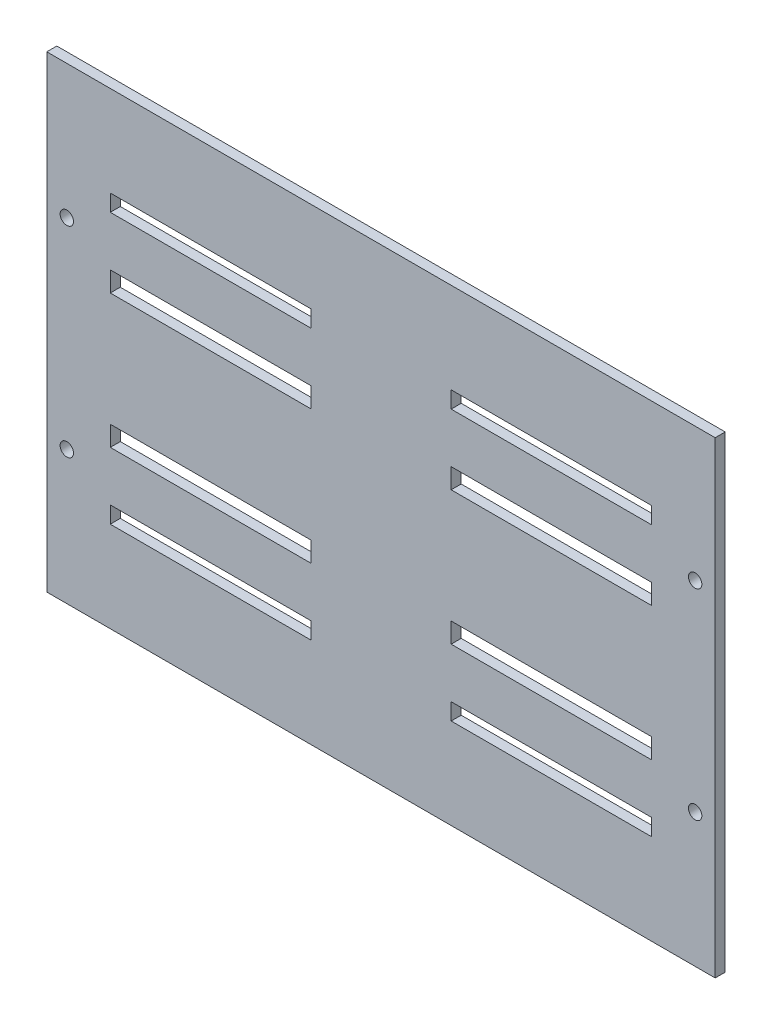
SolidWorks part; units mm, degrees
ref_plane "Front" through (0, 0, 0) normal (0, 0, 1) x (1, 0, 0)
ref_plane "Top" through (0, 0, 0) normal (0, 1, 0) x (1, 0, 0)
ref_plane "Right" through (0, 0, 0) normal (1, 0, 0) x (0, 0, -1)
sketch "草图2" plane through (0, 0, 0) normal (0, 0, 1) x (1, 0, 0)
  line L1 (-100, -70) -> (100, -70)
  line L2 (-100, -70) -> (-100, 70)
  line L3 (-100, 70) -> (100, 70)
  line L4 (100, -70) -> (100, 70)
  line L5 (-100, -70) -> (100, 70) construction
  line L6 (-100, 70) -> (100, -70) construction
  point P0 (0, 0)
  dimension "D1" = 140
  dimension "D2" = 200
extrude "凸台-拉伸1" add sketch "草图2" along normal blind 3
sketch "草图3" plane through (0, 0, 3) normal (0, 0, 1) x (1, 0, 0)
  line L0 (94, -30) -> (94, 30) construction
  line L2 (100, -70) -> (100, 70) construction
  circle A0 centre (94, 30) radius 2
  circle A1 centre (94, -30) radius 2
  point P4 (94, 0)
  dimension "D1" = 4
  dimension "D2" = 60
  dimension "D3" = 6
extrude "切除-拉伸1" cut sketch "草图3" against normal blind 3 contours A0 | A1
sketch "草图4" plane through (0, 0, 3) normal (0, 0, 1) x (1, 0, 0)
  line L0 (-100, 0) -> (100, 0) construction
  line L1 (-100, 70) -> (-100, -70) construction
  line L2 (100, -70) -> (100, 70) construction
  line L4 (21, 23) -> (81, 23)
  line L5 (21, 23) -> (21, 17)
  line L6 (21, 17) -> (81, 17)
  line L7 (81, 23) -> (81, 17)
  line L8 (21, 23) -> (81, 17) construction
  line L9 (21, 17) -> (81, 23) construction
  line L10 (21, -23) -> (81, -23)
  line L11 (21, -23) -> (21, -17)
  line L12 (21, -17) -> (81, -17)
  line L13 (81, -23) -> (81, -17)
  line L14 (21, -23) -> (81, -17) construction
  line L15 (21, -17) -> (81, -23) construction
  point P6 (51, 20)
  point P11 (51, -20)
  dimension "D1" = 34
  dimension "D2" = 6
  dimension "D3" = 6
  dimension "D4" = 17
  dimension "D5" = 60
  dimension "D6" = 19
extrude "切除-拉伸2" cut sketch "草图4" against normal blind 10
sketch "草图5" plane through (0, 0, 0) normal (0, 0, -1) x (-1, 0, 0)
  line L0 (-21, 17) -> (-21, 23) construction
  line L1 (-81, 37.9088) -> (-21, 37.9088)
  line L2 (-81, 37.9088) -> (-81, 42.9088)
  line L3 (-81, 42.9088) -> (-21, 42.9088)
  line L4 (-21, 37.9088) -> (-21, 42.9088)
  line L5 (-81, 37.9088) -> (-21, 42.9088) construction
  line L6 (-81, 42.9088) -> (-21, 37.9088) construction
  line L7 (-81, 23) -> (-81, 17) construction
  point P0 (-51, 40.4088)
  dimension "D1" = 5
extrude "切除-拉伸3" cut sketch "草图5" against normal blind 6
mirror "镜向1" about plane through (0, 0, 0) normal (0, 1, 0) of "切除-拉伸3"
ref_plane "基准面1" through (0, 0, 0) normal (-1, 0, 0) x (0, 0, 1)
mirror "镜向2" about plane through (0, 0, 0) normal (-1, 0, 0) of "切除-拉伸1", "镜向1", "切除-拉伸2", "切除-拉伸3"
